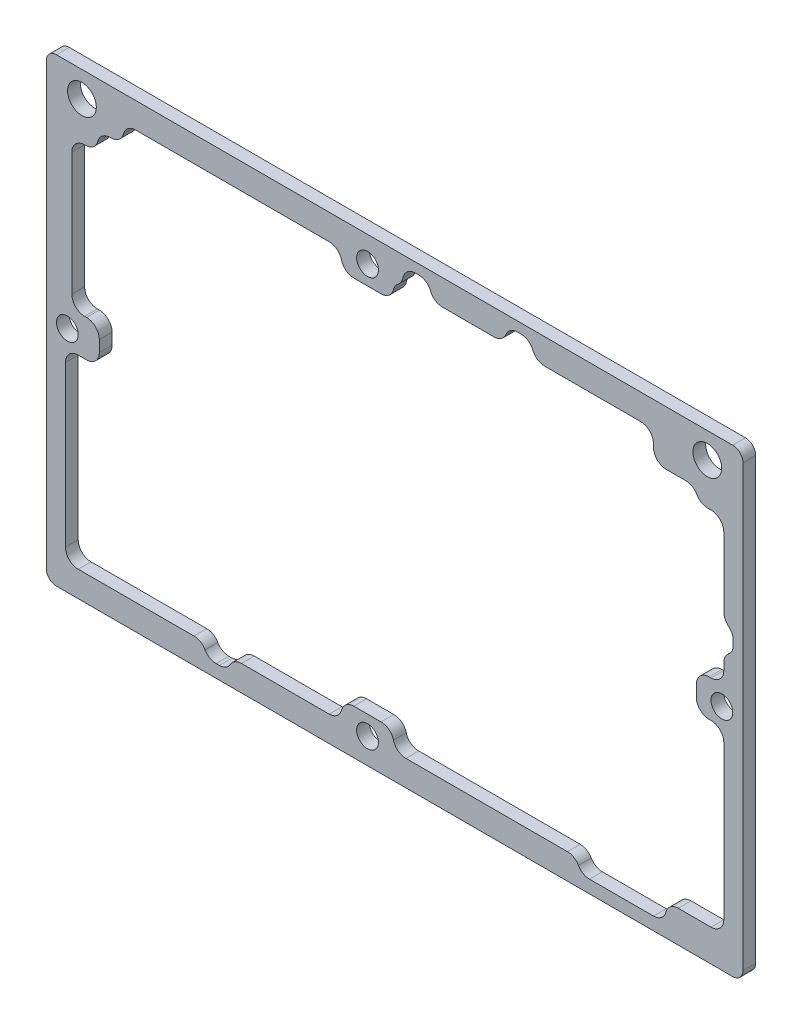
SolidWorks part; units mm, degrees
material "ABS PC"
ref_plane "Front Plane" through (0, 0, 0) normal (0, 0, 1) x (1, 0, 0)
ref_plane "Top Plane" through (0, 0, 0) normal (0, 1, 0) x (1, 0, 0)
ref_plane "Right Plane" through (0, 0, 0) normal (1, 0, 0) x (0, 0, -1)
sketch "Sketch1" plane through (0, 0, 0) normal (0, 0, 1) x (1, 0, 0)
  line L0 (94.968, 16.637) -> (-44.732, 16.637) construction
  line L1 (-61.4007, -97.663) -> (111.6368, -97.663)
  line L2 (-61.4007, -97.663) -> (-61.4007, 16.637)
  line L3 (-61.4007, 16.637) -> (111.6368, 16.637)
  line L4 (111.6368, -97.663) -> (111.6368, 16.637)
  line L5 (-61.4007, -97.663) -> (111.6368, 16.637) construction
  line L6 (-61.4007, 16.637) -> (111.6368, -97.663) construction
  point P4 (25.118, -40.513)
extrude "Boss-Extrude1" add sketch "Sketch1" along normal blind 3.175
sketch "Sketch3" plane through (0, 0, 3.175) normal (0, 0, 1) x (1, 0, 0)
  circle A0 centre (100.302, -26.543) radius 3.175
  circle A1 centre (99.413, -51.6255) radius 3.7703
  circle A2 centre (-47.907, -51.6255) radius 3.7703
  circle A3 centre (-47.907, -6.5405) radius 3.7703
  dimension "D1" = 6.35
  dimension "D2" = 7.5406
extrude "Cut-Extrude1" cut sketch "Sketch3" against normal through all
hole_wizard "#6 Clearance Hole1" positions "Sketch5" profile "Sketch4" hole size "#6" standard "ANSI Inch" end condition through all
sketch "Sketch5" plane through (0, 0, 3.175) normal (0, 0, 1) x (1, 0, 0)
  point P0 (18.387, 10.287)
  point P3 (-56.162, -40.894)
  point P6 (106.398, -40.894)
  point P9 (18.387, -91.313)
sketch "Sketch4" plane through (18.387, 10.287, 3.175) normal (1, 0, 0) x (0, -1, 0)
  line L0 (0, 0) -> (0, 3.175)
  line L1 (0, 3.175) -> (2.1526, 3.175)
  line L2 (2.1526, 3.175) -> (2.1526, 0)
  line L5 (2.1526, 0) -> (0, 0)
  line L11 (0, -6.35) -> (0, 107.95) construction
  dimension "Thru Hole Dia." = 4.3053
  dimension "Thru Hole Depth" = 3.175
hole_wizard "#2 Clearance Hole1" [suppressed] positions "Sketch7" profile "Sketch6" hole size "#2" standard "ANSI Inch"
sketch "Sketch7" plane through (0, 0, 3.175) normal (0, 0, 1) x (1, 0, 0)
  point P0 (26.788, 12.7)
  point P3 (89.488, 12.7)
  point P6 (89.488, -18.6)
  point P9 (26.788, -18.6)
sketch "Sketch6" plane through (26.788, 12.7, 3.175) normal (1, 0, 0) x (0, -1, 0)
  line L0 (0, 0) -> (0, 3.175)
  line L1 (0, 3.175) -> (1.3525, 3.175)
  line L2 (1.3525, 3.175) -> (1.3525, 0)
  line L5 (1.3525, 0) -> (0, 0)
  line L11 (0, -6.35) -> (0, 107.95) construction
  dimension "Thru Hole Dia." = 2.7051
  dimension "Thru Hole Depth" = 3.175
sketch "Sketch8" [suppressed] plane through (0, 0, 3.175) normal (0, 0, 1) x (1, 0, 0)
  line L9 (92.658, -23.1276) -> (22.2605, -23.1276)
  line L10 (22.2605, -23.1276) -> (22.2605, 6.5468)
  line L11 (22.2605, 6.5468) -> (14.6469, 6.5468)
  line L12 (92.658, -23.1276) -> (92.658, -32.1509)
  line L13 (28.768, 10.37) -> (28.768, -16.62)
  line L14 (28.768, -16.62) -> (87.508, -16.62)
  line L15 (87.508, -16.62) -> (87.508, 10.37)
  line L16 (87.508, 10.37) -> (28.768, 10.37)
  line L17 (28.768, 10.37) -> (28.768, -16.62)
  line L18 (28.768, -16.62) -> (87.508, -16.62)
  line L19 (87.508, -16.62) -> (87.508, 10.37)
  line L20 (87.508, 10.37) -> (28.768, 10.37)
  line L21 (92.658, -32.1509) -> (101.0704, -32.1509)
  line L22 (101.0704, -32.1509) -> (101.0704, -45.0855)
  line L23 (101.0704, -45.0855) -> (92.658, -45.0855)
  line L24 (92.658, -45.0855) -> (92.658, -58.1655)
  line L25 (92.658, -58.1655) -> (105.2868, -58.1655)
  line L26 (105.2868, -58.1655) -> (105.2868, -88.138)
  line L27 (105.2868, -88.138) -> (13.0594, -88.138)
  line L28 (13.0594, -88.138) -> (13.0594, -91.313)
  line L29 (13.0594, -91.313) -> (-55.0507, -91.313)
  line L30 (-55.0507, -91.313) -> (-55.0507, -58.1655)
  line L31 (-55.0507, -58.1655) -> (-41.367, -58.1655)
  line L32 (-41.367, -58.1655) -> (-41.367, -45.0855)
  line L33 (-41.367, -45.0855) -> (-50.8343, -45.0855)
  line L34 (-50.8343, -45.0855) -> (-50.8343, -35.5664)
  line L35 (-50.8343, -35.5664) -> (-55.0507, -35.5664)
  line L36 (-55.0507, -35.5664) -> (-55.0507, -13.0805)
  line L37 (-55.0507, -13.0805) -> (-41.367, -13.0805)
  line L38 (-41.367, -13.0805) -> (-41.367, 10.287)
  line L39 (14.6469, 6.5468) -> (14.6469, 10.287)
  line L40 (14.6469, 10.287) -> (-41.367, 10.287)
  line L44 (111.6368, -97.663) -> (111.6368, 16.637) construction
  line L45 (-61.4007, -97.663) -> (111.6368, -97.663) construction
  line L46 (-61.4007, 16.637) -> (-61.4007, -97.663) construction
  line L47 (111.6368, 16.637) -> (-61.4007, 16.637) construction
  circle A1 centre (106.398, -40.894) radius 2.1526 construction
  circle A3 centre (18.387, -91.313) radius 2.1526 construction
  circle A8 centre (-56.162, -40.894) radius 2.1526 construction
  circle A11 centre (18.387, 10.287) radius 2.1526 construction
  circle A13 centre (26.788, -18.6) radius 1.3525 construction
  dimension "D1" = 1.27
  dimension "D10" = 1.5875
  dimension "D2" = 3.175
  dimension "D3" = 6.35
  dimension "D4" = 9.525
  dimension "D5" = 3.175
  dimension "D6" = 6.35
  dimension "D7" = 6.35
  dimension "D8" = 3.175
  dimension "D9" = 3.175
  dimension "D11" = 1.5875
  dimension "D12" = 6.35
  dimension "D13" = 3.175
  dimension "D14" = 3.175
extrude "Cut-Extrude2" [suppressed] cut sketch "Sketch8" against normal through all contours L19 L20 L17 L18 | L39 L40 L38 L37 L36 L35 L34 L33 L32 L31 L30 L29 L28 L27 L26 L25 L24 L23 L22 L21 L12 L9 L10 L11
hole_wizard "#3 (0.213) Diameter Hole1" positions "3DSketch1" profile "Sketch9" hole size "#3" standard "ANSI Inch" end condition through all
sketch3d "3DSketch1"
  line L0 (18.387, 10.287, 0) -> (18.387, 10.287, 3.175) construction
  line L1 (-56.162, -40.894, 0) -> (-56.162, -40.894, 3.175) construction
  line L2 (18.387, -91.313, 0) -> (18.387, -91.313, 3.175) construction
  line L3 (106.398, -40.894, 0) -> (106.398, -40.894, 3.175) construction
  point P0 (18.387, 10.287, 3.175)
  point P5 (-56.162, -40.894, 3.175)
  point P9 (18.387, -91.313, 3.175)
  point P13 (106.398, -40.894, 3.175)
sketch "Sketch9" plane through (18.387, 10.287, 3.175) normal (1, 0, 0) x (0, -1, 0)
  line L0 (0, 0) -> (0, 3.175)
  line L1 (0, 3.175) -> (2.7051, 3.175)
  line L2 (2.7051, 3.175) -> (2.7051, 0)
  line L5 (2.7051, 0) -> (0, 0)
  line L11 (0, -6.35) -> (0, 107.95) construction
  dimension "Thru Hole Dia." = 5.4102
  dimension "Thru Hole Depth" = 3.175
hole_wizard "Ø3.0 (3) Diameter Hole1" [suppressed] positions "Sketch11" profile "Sketch10" hole size "Ø3.0" standard "ANSI Metric"
sketch "Sketch11" [suppressed] plane through (0, 0, 3.175) normal (0, 0, 1) x (1, 0, 0)
  point P0 (26.788, 12.7)
  point P3 (89.488, 12.7)
  point P6 (89.488, -18.6)
  point P9 (26.788, -18.6)
sketch "Sketch10" plane through (26.788, 12.7, 3.175) normal (1, 0, 0) x (0, -1, 0)
  line L0 (0, 0) -> (0, 3.175)
  line L1 (0, 3.175) -> (1.5, 3.175)
  line L2 (1.5, 3.175) -> (1.5, 0)
  line L5 (1.5, 0) -> (0, 0)
  line L11 (0, -6.35) -> (0, 107.95) construction
  dimension "Thru Hole Dia." = 3
  dimension "Thru Hole Depth" = 3.175
fillet "Fillet1" [suppressed] radius 1.27
fillet "Fillet2" [suppressed] radius 2.54
hole_wizard "1/4 Clearance Hole1" positions "Sketch12" profile "Sketch13" hole size "1/4" standard "ANSI Inch" end condition up to next
sketch "Sketch12" plane through (0, 0, 0) normal (0, 0, -1) x (-1, 0, 0)
  point P0 (-102.7785, 10.287)
  point P2 (52.5425, 10.287)
sketch "Sketch13" plane through (102.7785, 10.287, 0) normal (1, 0, 0) x (0, 1, 0)
  line L0 (0, 0) -> (0, 3.175)
  line L1 (0, 3.175) -> (3.5712, 3.175)
  line L2 (3.5712, 3.175) -> (3.5712, 0)
  line L5 (3.5712, 0) -> (0, 0)
  line L11 (0, -6.35) -> (0, 107.95) construction
  dimension "Thru Hole Dia." = 7.1425
  dimension "Thru Hole Depth" = 3.175
sketch "Sketch14" plane through (0, 0, 0) normal (0, 0, -1) x (-1, 0, 0)
  line L0 (-111.6368, -97.663) -> (-111.6368, 16.637) construction
  line L1 (-111.6368, 0.762) -> (-108.4618, 0.762)
  line L2 (-111.6368, 0.762) -> (-111.6368, 16.637)
  line L3 (-111.6368, 16.637) -> (-108.4618, 16.637)
  line L4 (-108.4618, 0.762) -> (-108.4618, 16.637)
  line L5 (-111.6368, 16.637) -> (61.4007, 16.637) construction
  line L6 (-25.118, -97.663) -> (-25.118, 16.637) construction
  line L7 (61.4007, -97.663) -> (-111.6368, -97.663) construction
  line L8 (58.2257, 0.762) -> (58.2257, 16.637)
  line L9 (61.4008, 16.637) -> (58.2257, 16.637)
  line L10 (61.4008, 0.762) -> (61.4008, 16.637)
  line L11 (61.4008, 0.762) -> (58.2257, 0.762)
  dimension "D1" = 3.175
  dimension "D2" = 15.875
extrude "Cut-Extrude3" [suppressed] cut sketch "Sketch14" against normal up to next
fillet "Fillet3" [suppressed] radius 1.5875
fillet "Fillet4" [suppressed] radius 2.54
sketch "Sketch15" [suppressed] plane through (0, 0, 0) normal (0, 0, -1) x (-1, 0, 0)
  line L0 (-28.768, -16.62) -> (-87.508, -16.62) construction
  line L1 (-90.988, 10.37) -> (-25.288, 10.37)
  line L2 (-90.988, 10.37) -> (-90.988, -16.62)
  line L3 (-90.988, -16.62) -> (-25.288, -16.62)
  line L4 (-25.288, 10.37) -> (-25.288, -16.62)
  line L5 (-87.508, 10.37) -> (-28.768, 10.37) construction
  line L6 (-90.988, 12.7) -> (-90.988, -18.6) construction
  line L7 (-25.288, 12.7) -> (-25.288, -18.6) construction
  circle A0 centre (-89.488, 12.7) radius 1.5 construction
  circle A1 centre (-89.488, -18.6) radius 1.5 construction
  circle A2 centre (-26.788, 12.7) radius 1.5 construction
  circle A3 centre (-26.788, -18.6) radius 1.5 construction
  dimension "D1" = 65.7
extrude "Cut-Extrude4" [suppressed] cut sketch "Sketch15" against normal up to next
sketch "Sketch16" plane through (0, 0, 0) normal (0, 0, -1) x (-1, 0, 0)
  circle A0 centre (-98.1425, -57.4894) radius 1.1906
  circle A1 centre (49.1775, -57.4894) radius 1.1906
  circle A2 centre (49.1775, -12.4044) radius 1.1906
  dimension "D1" = 2.3813
extrude "Cut-Extrude5" cut sketch "Sketch16" against normal up to next
sketch "Sketch17" plane through (0, 0, 0) normal (0, 0, -1) x (-1, 0, 0)
  line L0 (-111.6368, -97.663) -> (-111.6368, 16.637) construction
  line L1 (-89.4118, 10.287) -> (-59.6805, 10.287)
  line L2 (-89.4118, 10.287) -> (-89.4118, 3.175)
  line L3 (-70.3618, -91.313) -> (-24.737, -91.313)
  line L4 (-24.737, 10.287) -> (-24.737, -91.313) construction
  line L5 (61.4007, -97.663) -> (-111.6368, -97.663) construction
  line L6 (-111.6368, 16.637) -> (61.4007, 16.637) construction
  line L7 (61.4007, 16.637) -> (61.4007, -97.663) construction
  line L8 (-12.037, 10.287) -> (42.3507, 10.287)
  line L9 (-12.037, 10.287) -> (-12.037, -91.313) construction
  line L10 (-12.037, -91.313) -> (15.2495, -91.313)
  line L11 (42.3507, 10.287) -> (42.3507, 5.5245)
  line L12 (-24.737, 5.5245) -> (-12.037, 5.5245)
  line L13 (-24.737, 5.5245) -> (-24.737, 10.287)
  line L14 (-12.037, 5.5245) -> (-12.037, 10.287)
  line L15 (-24.737, -86.5505) -> (-12.037, -86.5505)
  line L16 (-24.737, -86.5505) -> (-24.737, -91.313)
  line L17 (-12.037, -86.5505) -> (-12.037, -91.313)
  line L18 (-92.5868, -89.7255) -> (-92.5867, -94.488)
  line L21 (-92.5867, -94.488) -> (-70.3618, -94.488)
  line L22 (-70.3618, -91.313) -> (-70.3618, -94.488)
  line L23 (-100.048, -45.2603) -> (-106.8743, -45.2603)
  line L25 (-92.5868, -89.7255) -> (-106.8743, -89.7255)
  line L26 (-106.8743, -45.2603) -> (-106.8743, -89.7255)
  line L27 (-111.6368, -97.663) -> (-111.6368, 16.637) construction
  line L28 (-18.387, 10.287) -> (-18.387, -91.313) construction
  line L32 (56.6382, -91.313) -> (56.6382, -45.2603)
  line L33 (56.6382, -45.2603) -> (48.2245, -45.2603)
  line L34 (48.7007, 0.762) -> (55.0507, 0.762)
  line L35 (55.0507, 0.762) -> (55.0507, -36.1315)
  line L36 (55.0507, -36.1315) -> (48.2245, -36.1315)
  line L37 (48.2245, -36.1315) -> (48.2245, -45.2603)
  line L39 (-106.8743, 0) -> (-106.8743, -23.4315)
  line L40 (-106.8743, -36.1315) -> (-100.048, -36.1315)
  line L41 (-100.048, -36.1315) -> (-100.048, -45.2603)
  line L42 (-106.8743, -28.194) -> (-106.8743, -36.1315)
  line L43 (-106.8743, -23.4315) -> (-109.2238, -23.4315)
  line L45 (-106.8743, -28.194) -> (-109.2238, -28.194)
  line L46 (-109.2238, -23.4315) -> (-109.2238, -28.194)
  line L47 (-99.7292, 0) -> (-106.8743, 0)
  line L49 (-99.7292, 0) -> (-99.7292, 3.175)
  line L50 (-99.7292, 3.175) -> (-89.4118, 3.175)
  line L52 (-27.1355, 10.287) -> (-24.737, 10.287)
  line L54 (-59.6805, 10.287) -> (-59.6805, 14.257)
  line L55 (-59.6805, 14.257) -> (-52.5355, 14.257)
  line L56 (-52.5355, 10.287) -> (-52.5355, 14.257)
  line L58 (-34.2805, 10.287) -> (-34.2805, 14.257)
  line L59 (-34.2805, 14.257) -> (-27.1355, 14.257)
  line L60 (-27.1355, 10.287) -> (-27.1355, 14.257)
  line L61 (-52.5355, 10.287) -> (-34.2805, 10.287)
  line L62 (22.3945, -91.313) -> (56.6382, -91.313)
  line L63 (42.3507, 5.5245) -> (48.7007, 5.5245)
  line L66 (48.7007, 5.5245) -> (48.7007, 0.762)
  line L68 (15.2495, -91.313) -> (15.2495, -94.488)
  line L69 (15.2495, -94.488) -> (22.3945, -94.488)
  line L70 (22.3945, -91.313) -> (22.3945, -94.488)
  circle A0 centre (-18.387, -91.313) radius 2.7051 construction
  circle A1 centre (56.162, -40.894) radius 2.7051 construction
  circle A2 centre (-18.387, 10.287) radius 2.7051 construction
  circle A3 centre (-106.398, -40.894) radius 2.7051 construction
  point P35 (-18.387, 10.287)
  dimension "D8" = 4.7625
  dimension "D16" = 4.7625
  dimension "D20" = 7.9375
  dimension "D21" = 4.7625
  dimension "D2" = 6.35
  dimension "D3" = 6.35
  dimension "D4" = 6.35
  dimension "D5" = 6.35
  dimension "D6" = 19.05
  dimension "D7" = 4.7625
  dimension "D9" = 3.175
  dimension "D10" = 22.225
  dimension "D11" = 7.9375
  dimension "D12" = 4.7625
  dimension "D13" = 4.3663
  dimension "D14" = 19.05
  dimension "D15" = 22.225
  dimension "D17" = 4.7625
  dimension "D18" = 6.35
  dimension "D19" = 15.875
  dimension "D22" = 4.7625
  dimension "D23" = 6.35
  dimension "D24" = 2.3495
  dimension "D25" = 7.9375
  dimension "D26" = 4.7625
  dimension "D27" = 13.462
  dimension "D28" = 7.145
  dimension "D29" = 3.175
  dimension "D30" = 3.97
  dimension "D31" = 7.145
  dimension "D32" = 51.9562
  dimension "D33" = 25.4
  dimension "D34" = 4.7625
  dimension "D35" = 6.35
  dimension "D36" = 39.0062
  dimension "D37" = 3.175
extrude "Cut-Extrude6" cut sketch "Sketch17" against normal through all
fillet "Fillet5" radius 3.175 27 edges at (99.7292, 0, 1.5875) (106.8743, 0, 1.5875) (106.8743, -23.4315, 1.5875) (106.8743, -28.194, 1.5875) (106.8743, -45.2603, 1.5875) (106.8743, -36.1315, 1.5875) (106.8743, -89.7255, 1.5875) (92.5867, -94.488, 1.5875) (70.3618, -94.488, 1.5875) (24.737, -91.313, 1.5875) (12.037, -91.313, 1.5875) (-15.2495, -94.488, 1.5875) (-22.3945, -94.488, 1.5875) (-56.6382, -91.313, 1.5875) (-55.0507, -36.1315, 1.5875) (-56.6382, -45.2603, 1.5875) (-55.0507, 0.762, 1.5875) (-48.7007, 5.5245, 1.5875) (-42.3507, 10.287, 1.5875) (12.037, 10.287, 1.5875) (24.737, 10.287, 1.5875) (34.2805, 14.257, 1.5875) (27.1355, 14.257, 1.5875) (52.5355, 14.257, 1.5875) (59.6805, 14.257, 1.5875) (89.4118, 10.287, 1.5875) (89.4118, 3.175, 1.5875)
fillet "Fillet6" radius 3.175 21 edges at (99.7292, 3.175, 1.5875) (59.6805, 10.287, 1.5875) (52.5355, 10.287, 1.5875) (34.2805, 10.287, 1.5875) (27.1355, 10.287, 1.5875) (24.737, 5.5245, 1.5875) (12.037, 5.5245, 1.5875) (-42.3507, 5.5245, 1.5875) (-48.7007, 0.762, 1.5875) (-48.2245, -36.1315, 1.5875) (-48.2245, -45.2603, 1.5875) (-22.3945, -91.313, 1.5875) (-15.2495, -91.313, 1.5875) (12.037, -86.5505, 1.5875) (24.737, -86.5505, 1.5875) (70.3618, -91.313, 1.5875) (92.5868, -89.7255, 1.5875) (100.048, -45.2603, 1.5875) (100.048, -36.1315, 1.5875) (109.2238, -28.194, 1.5875) (109.2238, -23.4315, 1.5875)
fillet "Fillet7" radius 2.54 4 edges at (111.6368, 16.637, 1.5875) (111.6368, -97.663, 1.5875) (-61.4007, -97.663, 1.5875) (-61.4007, 16.637, 1.5875)
